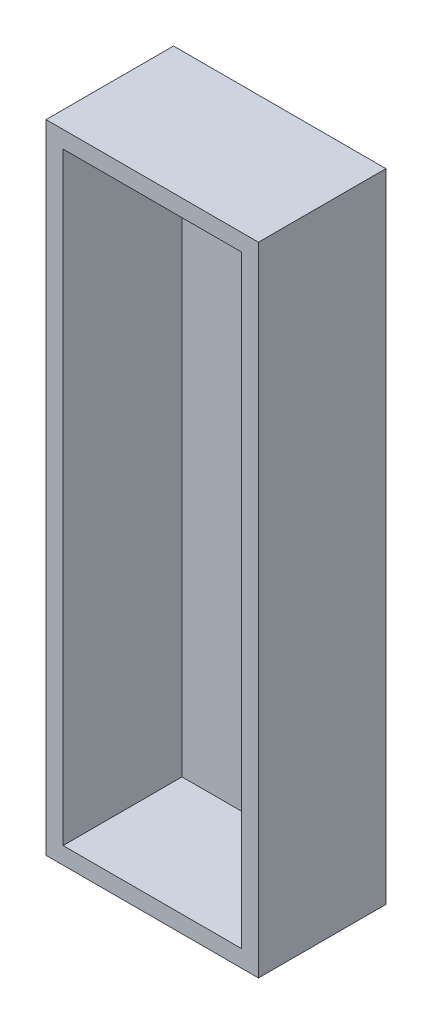
SolidWorks part; units mm, degrees
ref_plane "Alzado" through (0, 0, 0) normal (0, 0, 1) x (1, 0, 0)
ref_plane "Planta" through (0, 0, 0) normal (0, 1, 0) x (1, 0, 0)
ref_plane "Vista lateral" through (0, 0, 0) normal (1, 0, 0) x (0, 0, -1)
sketch "Croquis1" plane through (0, 0, 0) normal (0, 0, 1) x (1, 0, 0)
  line L1 (-25, -75) -> (25, -75)
  line L2 (-25, -75) -> (-25, 75)
  line L3 (-25, 75) -> (25, 75)
  line L4 (25, -75) -> (25, 75)
  line L5 (-25, -75) -> (25, 75) construction
  line L6 (-25, 75) -> (25, -75) construction
  point P0 (0, 0)
  dimension "D1" = 50
  dimension "D2" = 150
extrude "Saliente-Extruir1" add sketch "Croquis1" along normal blind 30
sketch "Croquis2" plane through (0, 0, 30) normal (0, 0, 1) x (1, 0, 0)
  line L1 (-21, -71) -> (21, -71)
  line L2 (-21, -71) -> (-21, 71)
  line L3 (-21, 71) -> (21, 71)
  line L4 (21, -71) -> (21, 71)
  line L5 (-21, -71) -> (21, 71) construction
  line L6 (-21, 71) -> (21, -71) construction
  point P0 (0, 0)
  dimension "D1" = 42
  dimension "D2" = 142
extrude "Cortar-Extruir1" cut sketch "Croquis2" against normal blind 28
